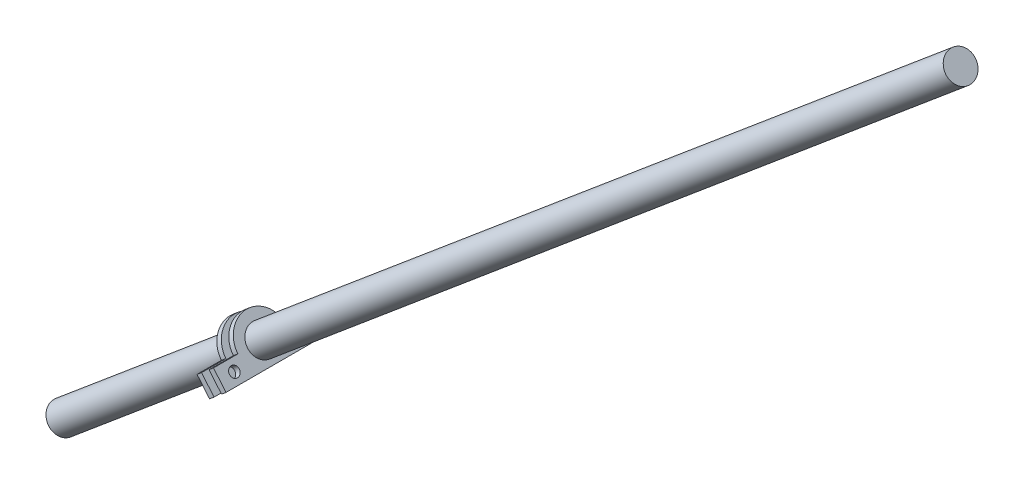
SolidWorks part; units mm, degrees
material "1.0045 (S355JR)"
ref_plane "Ön Düzlem" through (0, 0, 0) normal (0, 0, 1) x (1, 0, 0)
ref_plane "Üst Düzlem" through (0, 0, 0) normal (0, 1, 0) x (1, 0, 0)
ref_plane "Sağ Düzlem" through (0, 0, 0) normal (1, 0, 0) x (0, 0, -1)
sketch "Çizim1" plane through (0, 0, 0) normal (0, 0, 1) x (1, 0, 0)
  line L0 (0, 0) -> (459.6267, 385.6726)
  dimension "D1" = 600
sweep "Süpür1" add path "Çizim1" circular profile diameter 15 parameters "D3"=15
sketch "Çizim8" plane through (0, 0, 0) normal (-0.766, -0.6428, 0) x (0, 0, 1)
  line L0 (-25, -10) -> (25, -10)
  line L1 (25, -10) -> (25, 0)
  line L2 (25, 0) -> (12.5, 0)
  line L3 (0, 0) -> (0, 25.6111) construction
  line L4 (-25, 0) -> (-12.5, 0)
  line L5 (-25, -10) -> (-25, 0)
  circle A1 centre (17.5, -5) radius 2.5
  circle A2 centre (-17.5, -5) radius 2.5
  arc A3 (12.5, 0) -> (-12.5, 0) centre (0, 0) ccw
  point P11 (0, -10)
  dimension "D3" = 5
  dimension "D4" = 12.5
  dimension "D2" = 25
extrude "Yükseklik-Ekstrüzyon1" add sketch "Çizim8" along normal blind 3 from offset 125 offset against normal yes
extrude "Yükseklik-Ekstrüzyon2" add sketch "Çizim8<3>" along normal blind 3 from offset 133 offset against normal yes
sketch "Çizim8<3>" plane through (0, 0, 0) normal (-0.766, -0.6428, 0) x (0, 0, 1) same geometry as "Çizim8"
